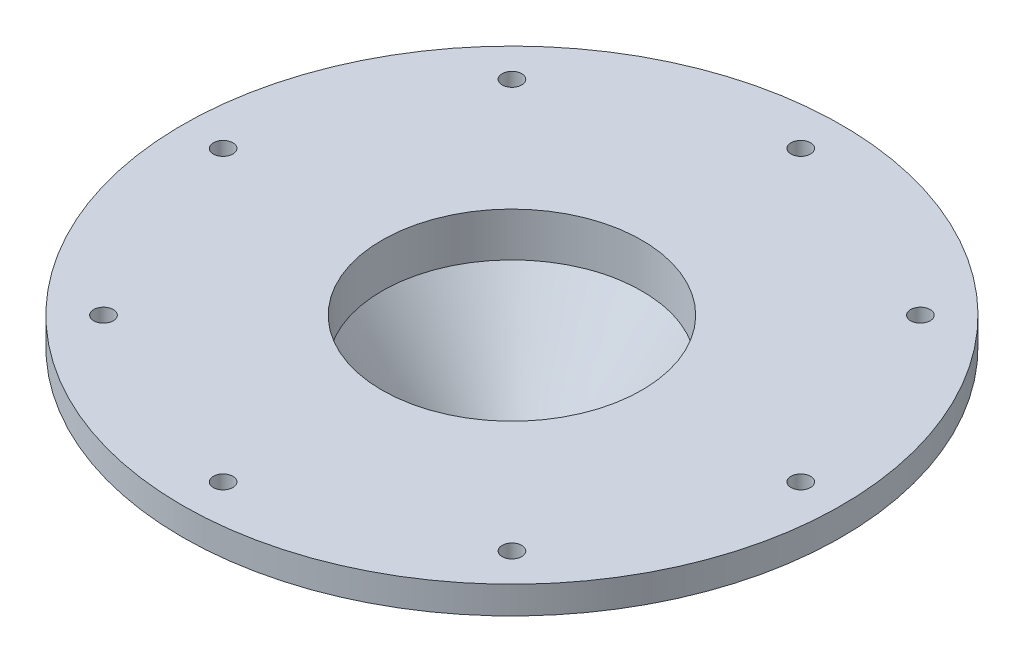
SolidWorks part; units mm, degrees
material "7075-T6 (SN)"
ref_plane "Front Plane" through (0, 0, 0) normal (0, 0, 1) x (1, 0, 0)
ref_plane "Top Plane" through (0, 0, 0) normal (0, 1, 0) x (1, 0, 0)
ref_plane "Right Plane" through (0, 0, 0) normal (1, 0, 0) x (0, 0, -1)
sketch "Sketch1" plane through (0, 0, 0) normal (0, 1, 0) x (1, 0, 0)
  circle A0 centre (0, 0) radius 38.0403
  dimension "D1" = 76.0806
extrude "Boss-Extrude1" add sketch "Sketch1" along normal blind 3.175
hole_wizard "Tap Drill for #4-40 Tap1" positions "Sketch3" profile "Sketch4" hole size "#4-40" standard "ANSI Inch" end condition through all
sketch "Sketch3" plane through (0, 0, 0) normal (0, -1, 0) x (-1, 0, 0)
  point P0 (0, -33.3375)
  dimension "D1" = 33.3375
sketch "Sketch4" plane through (0, 0, 33.3375) normal (1, 0, 0) x (0, 0, -1)
  line L0 (0, 0) -> (0, 3.175)
  line L1 (0, 3.175) -> (1.1303, 3.175)
  line L2 (1.1303, 3.175) -> (1.1303, 0)
  line L5 (1.1303, 0) -> (0, 0)
  line L11 (0, -6.35) -> (0, 107.95) construction
  dimension "Thru Hole Dia." = 2.2606
  dimension "Thru Hole Depth" = 3.175
pattern_circular "CirPattern1" count 8 over 360 about axis through (0, 0, 0) along (0, 1, 0) of "Tap Drill for #4-40 Tap1"
sketch "Sketch5" plane through (0, 0, 0) normal (0, -1, 0) x (1, 0, 0)
  circle A0 centre (0, 0) radius 25.4
  dimension "D1" = 50.8
extrude "Boss-Extrude2" add sketch "Sketch5" along normal blind 19.05
sketch "Sketch6" plane through (0, -19.05, 0) normal (0, -1, 0) x (1, 0, 0)
  circle A0 centre (0, 0) radius 5
  dimension "D1" = 10
extrude "Cut-Extrude1" cut sketch "Sketch6" against normal through all both and the other way through all
sketch "Sketch7" plane through (0, 3.175, 0) normal (0, 1, 0) x (1, 0, 0)
  circle A0 centre (0, 0) radius 15
  dimension "D1" = 30
extrude "Cut-Extrude2" cut sketch "Sketch7" against normal blind 5.08
sketch "Sketch8" plane through (0, -1.905, 0) normal (0, 1, 0) x (1, 0, 0)
  circle A0 centre (0, 0) radius 15
  circle A1 centre (0, 0) radius 15 construction
  dimension "D1" = 0
ref_plane "Plane1" through (0, -15.875, 0) normal (0, -1, 0) x (-1, 0, 0)
sketch "Sketch9" plane through (0, -15.875, 0) normal (0, -1, 0) x (-1, 0, 0)
  circle A0 centre (0, 0) radius 5
  circle A1 centre (0, 0) radius 5 construction
  dimension "D1" = 0
loft "Cut-Loft1" cut profiles "Sketch8", "Sketch9" connector at (0, -1.905, 15) connector at (-1.3659, -15.875, 4.8098)
sketch "Sketch10" plane through (0, 0, 0) normal (0, 0, 1) x (1, 0, 0)
  line L6 (0, 0) -> (0, -33.2378) construction
  line L7 (-25.4, 0) -> (-24.4, 0)
  line L8 (-25.4, 0) -> (25.4, 0) construction
  line L9 (-24.4, 0) -> (-8.4152, -19.05)
  line L10 (-25.4, -19.05) -> (25.4, -19.05) construction
  line L11 (-8.4152, -19.05) -> (-25.4, -19.05)
  line L12 (-25.4, -19.05) -> (-25.4, 0)
  dimension "D1" = 50
  dimension "D2" = 1
revolve "Cut-Revolve1" cut sketch "Sketch10" angle 360 about L6
